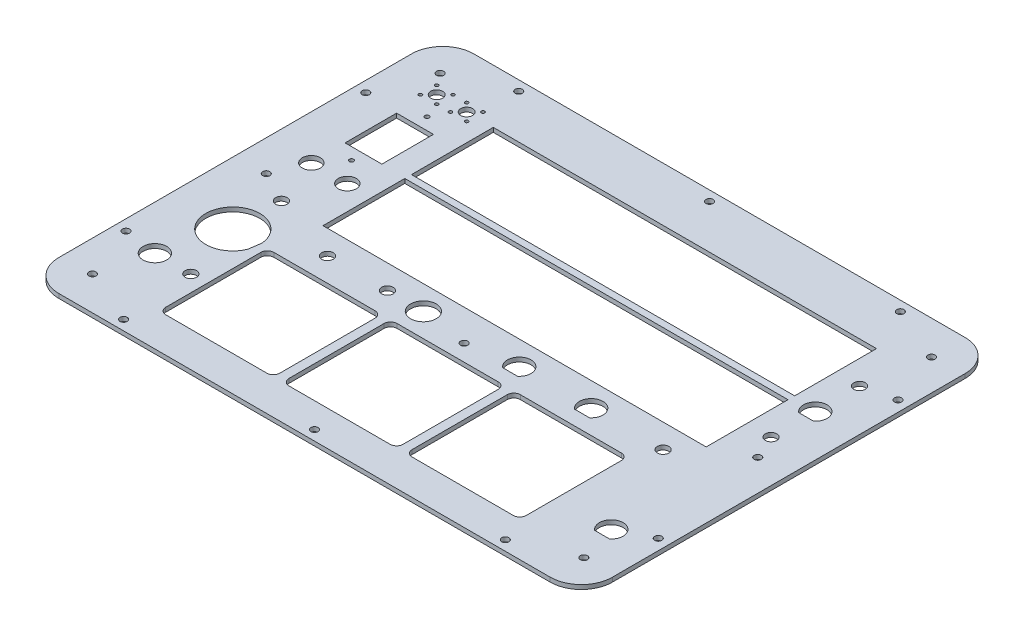
SolidWorks part; units mm, degrees
other "Markup1"
sketch "Sketch4" plane through (-146.6469, 2.286, -109.9312) normal (0, 1, 0) x (1, 0, 0)
other "DetailItem1"
other "DetailItem2"
other "DetailItem3"
other "Markup2"
sketch "Sketch5"
other "DetailItem4"
other "DetailItem5"
other "DetailItem6"
other "DetailItem7"
other "DetailItem8"
other "DetailItem9"
other "DetailItem1"
other "DetailItem2"
material "6061-T6 (SS)"
ref_plane "Front Plane" through (0, 0, 0) normal (0, 0, 1) x (1, 0, 0)
ref_plane "Top Plane" through (0, 0, 0) normal (0, 1, 0) x (1, 0, 0)
ref_plane "Right Plane" through (0, 0, 0) normal (1, 0, 0) x (0, 0, -1)
sketch "Sketch1" plane through (0, 0, 0) normal (0, 1, 0) x (1, 0, 0)
  line L1 (-146.6469, 109.9312) -> (146.6469, 109.9312)
  line L2 (-146.6469, 109.9312) -> (-146.6469, -109.9312)
  line L3 (-146.6469, -109.9312) -> (146.6469, -109.9312)
  line L4 (146.6469, 109.9312) -> (146.6469, -109.9312)
  line L5 (-146.6469, 109.9312) -> (146.6469, -109.9312) construction
  line L6 (-146.6469, -109.9312) -> (146.6469, 109.9312) construction
  point P0 (0, 0)
  dimension "D1" = 293.2938
  dimension "D2" = 219.8624
extrude "Boss-Extrude1" add sketch "Sketch1" along normal blind 2.286
fillet "Fillet1" radius 16.51 4 edges at (-146.6469, 1.143, -109.9312) (146.6469, 1.143, -109.9312) (-146.6469, 1.143, 109.9312) (146.6469, 1.143, 109.9312)
extrude "Cut-Extrude4" cut sketch "Sketch13" against normal through all
sketch "Sketch13" plane through (0, 2.286, -256.6474) normal (0, 1, 0) x (1, 0, 0)
  line L1 (-91.2749, -175.2912) -> (111.7219, -175.2912)
  line L2 (-91.2749, -175.2912) -> (-91.2749, -218.6236)
  line L3 (-91.2749, -218.6236) -> (111.7219, -218.6236)
  line L4 (111.7219, -175.2912) -> (111.7219, -218.6236)
  line L5 (-91.2749, -222.1636) -> (111.7219, -222.1636)
  line L6 (-91.2749, -222.1636) -> (-91.2749, -265.496)
  line L7 (-91.2749, -265.496) -> (111.7219, -265.496)
  line L8 (111.7219, -222.1636) -> (111.7219, -265.496)
sketch "Sketch3" plane through (0, 2.286, 0) normal (0, 1, 0) x (1, 0, 0)
  line L0 (111.7219, 34.4837) -> (124.4219, 36.2538) construction
  line L1 (124.4219, 36.2538) -> (111.7219, 38.0238) construction
  line L2 (-91.2749, -8.8487) -> (111.7219, -8.8487) construction
  line L3 (111.7219, 81.3562) -> (124.4219, 59.69) construction
  line L4 (124.4219, 59.69) -> (111.7219, 38.0238) construction
  line L5 (111.7219, 34.4837) -> (124.4219, 12.8175) construction
  line L6 (124.4219, 12.8175) -> (111.7219, -8.8487) construction
  line L7 (59.5622, -26.4001) -> (67.4378, -26.4001)
  line L12 (0, -1000) -> (0, 49000) construction
  line L13 (111.7219, 34.4837) -> (-91.2749, 34.4837) construction
  line L18 (21.4622, -26.4001) -> (29.3378, -26.4001)
  line L19 (120.4841, 31.4024) -> (128.3597, 31.4024)
  line L24 (120.4841, -76.6826) -> (128.3597, -76.6826)
  line L25 (-130.1369, -109.9312) -> (130.1369, -109.9312) construction
  line L26 (111.7219, -8.8487) -> (111.7219, 34.4837) construction
  arc A0 (128.3597, 31.4024) -> (120.4841, 31.4024) centre (124.4219, 36.2538) ccw
  circle A1 centre (124.4219, 59.69) radius 3.048
  circle A2 centre (124.4219, 12.8175) radius 3.048
  circle A3 centre (-76.2, -21.5487) radius 3.048
  circle A4 centre (-44.45, -21.5487) radius 3.048
  circle A5 centre (-25.4, -21.5487) radius 6.8
  arc A6 (128.3597, -76.6826) -> (120.4841, -76.6826) centre (124.4219, -71.8312) ccw
  arc A7 (29.3378, -26.4001) -> (21.4622, -26.4001) centre (25.4, -21.5487) ccw
  arc A8 (67.4378, -26.4001) -> (59.5622, -26.4001) centre (63.5, -21.5487) ccw
  circle A9 centre (25.4, -21.5487) radius 9.0043 construction
  circle A10 centre (63.5, -21.5487) radius 9.0043 construction
  circle A11 centre (101.6, -21.5487) radius 3.048
  point P20 (0, 0)
  point P44 (0, 0)
  dimension "D5" = 13.6
  dimension "D6" = 6.096
  dimension "D7" = 6.096
  dimension "D3" = 18.0086
  dimension "D4" = 12.4968
  dimension "D2" = 12.7
  dimension "D8" = 12.7
  dimension "D9" = 19.05
  dimension "D10" = 11.0998
  dimension "D11" = 25.4
  dimension "D12" = 38.1
  dimension "D13" = 38.1
  dimension "D14" = 38.1
  dimension "D15" = 76.2
  dimension "D16" = 25.4
sketch "Sketch8" plane through (0, 2.286, 0) normal (0, 1, 0) x (1, 0, 0)
  line L1 (-130.048, 99.441) -> (130.048, 99.441) construction
  line L2 (-135.89, 93.599) -> (-135.89, -93.599) construction
  line L3 (-130.048, -99.441) -> (130.048, -99.441) construction
  line L4 (135.89, 93.599) -> (135.89, -93.599) construction
  line L5 (-135.89, 99.441) -> (135.89, -99.441) construction
  line L6 (-135.89, -99.441) -> (135.89, 99.441) construction
  arc A0 (130.048, 99.441) -> (135.89, 93.599) centre (130.048, 93.599) cw construction
  arc A1 (130.048, -99.441) -> (135.89, -93.599) centre (130.048, -93.599) ccw construction
  arc A2 (-135.89, -93.599) -> (-130.048, -99.441) centre (-130.048, -93.599) ccw construction
  arc A3 (-130.048, 99.441) -> (-135.89, 93.599) centre (-130.048, 93.599) ccw construction
  point P0 (0, 0)
  dimension "D3" = 5.842
  dimension "D1" = 271.78
  dimension "D2" = 198.882
sketch "Sketch10" plane through (0, 2.286, 0) normal (0, 1, 0) x (1, 0, 0)
  line L2 (130.1369, 109.9312) -> (-130.1369, 109.9312) construction
  line L3 (-146.6469, 93.4212) -> (-146.6469, -93.4212) construction
  circle A0 centre (-121.2469, 81.3562) radius 3.175
  point P2 (-123.8756, 81.5186)
  dimension "D1" = 6.35
  dimension "D2" = 28.575
  dimension "D3" = 25.4
extrude "Cut-Extrude2" cut sketch "Sketch10" against normal through all
hole_wizard "#2-56 Tapped Hole1" positions "Sketch11" profile "Sketch12" tap size "#2-56" standard "ANSI Inch" end condition through all
sketch "Sketch11" plane through (0, 2.286, 0) normal (0, 1, 0) x (1, 0, 0)
  line L0 (-125.5649, 85.6742) -> (-116.9289, 77.0382) construction
  point P1 (-125.5649, 85.6742)
  point P2 (-116.9289, 77.0382)
  point P9 (-116.9289, 85.6742)
  point P11 (-125.5649, 77.0382)
  dimension "D1" = 8.636
  dimension "D2" = 8.636
sketch "Sketch12" plane through (-125.5649, 2.286, -85.6742) normal (1, 0, 0) x (0, 0, 1)
  line L0 (0, 0) -> (0, 2.286)
  line L1 (0, 2.286) -> (0.889, 2.286)
  line L2 (0.889, 2.286) -> (0.889, 0)
  line L5 (0.889, 0) -> (0, 0)
  line L11 (0, -6.35) -> (0, 107.95) construction
  dimension "Thru Tap Drill Dia." = 1.778
  dimension "Thru Tap Drill Depth" = 2.286
cosmetic thread "Hole Thread1" parameters "D2"=2.1844
cosmetic thread "Hole Thread2" parameters "D2"=2.1844
cosmetic thread "Hole Thread3" parameters "D2"=2.1844
cosmetic thread "Hole Thread4" parameters "D2"=2.1844
extrude "Cut-Extrude5" cut sketch "Sketch3" against normal through all
sketch "Sketch9" plane through (0, 2.286, 0) normal (0, 1, 0) x (1, 0, 0)
  line L1 (-130.048, 99.441) -> (130.048, 99.441) construction
  line L2 (-113.665, -1011.6034) -> (-113.665, 48988.3966) construction
  line L3 (-104.14, 16.891) -> (-113.665, 16.891) construction
  line L4 (-113.665, 16.891) -> (-123.19, 16.891) construction
  line L5 (-135.89, 93.599) -> (-135.89, -93.599) construction
  line L7 (-123.415, 62.291) -> (-103.915, 62.291)
  line L8 (-123.415, 62.291) -> (-123.415, 34.991)
  line L9 (-123.415, 34.991) -> (-103.915, 34.991)
  line L10 (-103.915, 62.291) -> (-103.915, 34.991)
  line L11 (-123.415, 62.291) -> (-103.915, 34.991) construction
  line L12 (-123.415, 34.991) -> (-103.915, 62.291) construction
  line L14 (-91.2749, -8.8487) -> (111.7219, -8.8487) construction
  line L15 (-99.4364, -32.9524) -> (-100.3898, -39.531)
  circle A0 centre (-123.19, 16.891) radius 4.7625
  circle A1 centre (-104.14, 16.891) radius 4.7625
  circle A2 centre (-113.665, -8.509) radius 3.048
  circle A3 centre (-76.2, -21.5487) radius 3.048 construction
  arc A5 (-99.4364, -32.9524) -> (-100.3898, -39.531) centre (-113.665, -34.2487) ccw
  circle A6 centre (-123.19, -65.9987) radius 6.2484
  circle A7 centre (25.4, -21.5487) radius 6.2484 construction
  circle A8 centre (-104.14, -65.9987) radius 3.048
  circle A9 centre (-44.45, -21.5487) radius 3.048 construction
  point P11 (-113.665, 48.641)
  point P34 (0, 0)
  point P35 (0, 0)
  dimension "D1" = 9.525
  dimension "D9" = 28.575
  dimension "D2" = 19.05
  dimension "D3" = 22.225
  dimension "D4" = 82.55
  dimension "D5" = 19.5
  dimension "D6" = 27.3
  dimension "D7" = 50.8
  dimension "D8" = 25.4
  dimension "D10" = 25.4
  dimension "D11" = 31.75
  dimension "D12" = 9.525
  dimension "D13" = 9.525
extrude "Cut-Extrude3" cut sketch "Sketch9" against normal through all
hole_wizard "#4-40 Tapped Hole1" positions "Sketch14" profile "Sketch15" tap size "#4-40" standard "ANSI Inch" end condition through all
sketch "Sketch14" plane through (0, 2.286, 0) normal (0, 1, 0) x (1, 0, 0)
  line L0 (-113.665, 28.641) -> (-113.665, 68.641)
  point P0 (-113.665, 28.641)
  point P2 (-113.665, 68.641)
  dimension "D1" = 40
sketch "Sketch15" plane through (-113.665, 2.286, -28.641) normal (1, 0, 0) x (0, 0, 1)
  line L0 (0, 0) -> (0, 2.286)
  line L1 (0, 2.286) -> (1.1303, 2.286)
  line L2 (1.1303, 2.286) -> (1.1303, 0)
  line L5 (1.1303, 0) -> (0, 0)
  line L11 (0, -6.35) -> (0, 107.95) construction
  dimension "Thru Tap Drill Dia." = 2.2606
  dimension "Thru Tap Drill Depth" = 2.286
cosmetic thread "Hole Thread9" parameters "D2"=2.8448
cosmetic thread "Hole Thread10" parameters "D2"=2.8448
hole_wizard "#6 Clearance Hole1" positions "Sketch16" profile "Sketch17" hole size "#6" standard "ANSI Inch" end condition through all
sketch "Sketch16" plane through (0, 2.286, -256.6474) normal (0, 1, 0) x (1, 0, 0)
  point P0 (0.0139, -152.0006)
  point P3 (-101.0781, -152.0006)
  point P6 (101.1059, -152.0006)
  point P9 (140.9839, -193.1486)
  point P12 (140.9839, -320.1486)
  point P15 (101.1059, -361.2966)
  point P18 (0.0139, -361.2966)
  point P21 (-101.0781, -361.2966)
  point P24 (-140.9561, -320.1486)
  point P27 (-140.9561, -193.1486)
sketch "Sketch17" plane through (0.0139, 2.286, -104.6468) normal (1, 0, 0) x (0, 0, 1)
  line L0 (0, 0) -> (0, 2.286)
  line L1 (0, 2.286) -> (1.8986, 2.286)
  line L2 (1.8986, 2.286) -> (1.8986, 0)
  line L3 (1.8986, 0) -> (0, 0)
  line L4 (0, -6.35) -> (0, 107.95) construction
  dimension "Thru Hole Dia." = 3.7973
  dimension "Thru Hole Depth" = 2.286
hole_wizard "#6 Clearance Hole2" positions "Sketch18" profile "Sketch19" hole size "#6" standard "ANSI Inch" end condition through all
sketch "Sketch18" plane through (0, 2.286, 0) normal (0, 1, 0) x (1, 0, 0)
  line L4 (-130.175, -92.075) -> (0, 0) construction
  line L5 (0, 0) -> (130.175, -92.075) construction
  line L7 (-130.175, 92.075) -> (0, 0) construction
  point P4 (-130.175, 0)
  point P21 (-130.175, -92.075)
  point P26 (-130.175, 92.075)
  point P28 (130.175, 92.075)
  point P30 (130.175, -92.075)
  point P58 (130.175, 0)
  point P60 (0, -25.4)
  dimension "D1" = 260.35
  dimension "D2" = 184.15
  dimension "D3" = 25.4
sketch "Sketch19" plane through (-130.175, 2.286, 0) normal (1, 0, 0) x (0, 0, 1)
  line L0 (0, 0) -> (0, 2.286)
  line L1 (0, 2.286) -> (1.8986, 2.286)
  line L2 (1.8986, 2.286) -> (1.8986, 0)
  line L5 (1.8986, 0) -> (0, 0)
  line L11 (0, -6.35) -> (0, 107.95) construction
  dimension "Thru Hole Dia." = 3.7973
  dimension "Thru Hole Depth" = 2.286
extrude "Cut-Extrude6" cut sketch "Sketch20" against normal through all
sketch "Sketch20" plane through (0, 2.286, -256.6474) normal (0, 1, 0) x (1, 0, 0)
  line L36 (-95.25, -294.1771) -> (-95.25, -344.5961) construction
  line L37 (-92.075, -347.7711) -> (-38.481, -347.7711) construction
  line L38 (-35.306, -344.5961) -> (-35.306, -294.1771) construction
  line L39 (-38.481, -291.0021) -> (-92.075, -291.0021) construction
  line L40 (-29.972, -294.1771) -> (-29.972, -344.5961) construction
  line L41 (26.797, -291.0021) -> (-26.797, -291.0021) construction
  line L42 (29.972, -344.5961) -> (29.972, -294.1771) construction
  line L43 (-26.797, -347.7711) -> (26.797, -347.7711) construction
  line L44 (35.306, -294.1771) -> (35.306, -344.5961) construction
  line L45 (92.075, -291.0021) -> (38.481, -291.0021) construction
  line L46 (95.25, -344.5961) -> (95.25, -294.1771) construction
  line L47 (38.481, -347.7711) -> (92.075, -347.7711) construction
  line L48 (-95.504, -294.1771) -> (-95.504, -344.5961)
  line L49 (-92.075, -348.0251) -> (-38.481, -348.0251)
  line L50 (-35.052, -344.5961) -> (-35.052, -294.1771)
  line L51 (-38.481, -290.7481) -> (-92.075, -290.7481)
  line L52 (-30.226, -294.1771) -> (-30.226, -344.5961)
  line L53 (-26.797, -348.0251) -> (26.797, -348.0251)
  line L54 (30.226, -344.5961) -> (30.226, -294.1771)
  line L55 (26.797, -290.7481) -> (-26.797, -290.7481)
  line L56 (35.052, -294.1771) -> (35.052, -344.5961)
  line L57 (38.481, -348.0251) -> (92.075, -348.0251)
  line L58 (95.504, -344.5961) -> (95.504, -294.1771)
  line L59 (92.075, -290.7481) -> (38.481, -290.7481)
  arc A36 (-92.075, -291.0021) -> (-95.25, -294.1771) centre (-92.075, -294.1771) ccw construction
  arc A37 (-95.25, -344.5961) -> (-92.075, -347.7711) centre (-92.075, -344.5961) ccw construction
  arc A38 (-38.481, -347.7711) -> (-35.306, -344.5961) centre (-38.481, -344.5961) ccw construction
  arc A39 (-35.306, -294.1771) -> (-38.481, -291.0021) centre (-38.481, -294.1771) ccw construction
  arc A40 (-26.797, -291.0021) -> (-29.972, -294.1771) centre (-26.797, -294.1771) ccw construction
  arc A41 (-29.972, -344.5961) -> (-26.797, -347.7711) centre (-26.797, -344.5961) ccw construction
  arc A42 (29.972, -294.1771) -> (26.797, -291.0021) centre (26.797, -294.1771) ccw construction
  arc A43 (26.797, -347.7711) -> (29.972, -344.5961) centre (26.797, -344.5961) ccw construction
  arc A44 (35.306, -344.5961) -> (38.481, -347.7711) centre (38.481, -344.5961) ccw construction
  arc A45 (38.481, -291.0021) -> (35.306, -294.1771) centre (38.481, -294.1771) ccw construction
  arc A46 (95.25, -294.1771) -> (92.075, -291.0021) centre (92.075, -294.1771) ccw construction
  arc A47 (92.075, -347.7711) -> (95.25, -344.5961) centre (92.075, -344.5961) ccw construction
  arc A48 (-95.504, -344.5961) -> (-92.075, -348.0251) centre (-92.075, -344.5961) ccw
  arc A49 (-38.481, -348.0251) -> (-35.052, -344.5961) centre (-38.481, -344.5961) ccw
  arc A50 (-35.052, -294.1771) -> (-38.481, -290.7481) centre (-38.481, -294.1771) ccw
  arc A51 (-92.075, -290.7481) -> (-95.504, -294.1771) centre (-92.075, -294.1771) ccw
  arc A52 (-30.226, -344.5961) -> (-26.797, -348.0251) centre (-26.797, -344.5961) ccw
  arc A53 (26.797, -348.0251) -> (30.226, -344.5961) centre (26.797, -344.5961) ccw
  arc A54 (30.226, -294.1771) -> (26.797, -290.7481) centre (26.797, -294.1771) ccw
  arc A55 (-26.797, -290.7481) -> (-30.226, -294.1771) centre (-26.797, -294.1771) ccw
  arc A56 (35.052, -344.5961) -> (38.481, -348.0251) centre (38.481, -344.5961) ccw
  arc A57 (92.075, -348.0251) -> (95.504, -344.5961) centre (92.075, -344.5961) ccw
  arc A58 (95.504, -294.1771) -> (92.075, -290.7481) centre (92.075, -294.1771) ccw
  arc A59 (38.481, -290.7481) -> (35.052, -294.1771) centre (38.481, -294.1771) ccw
pattern_linear "LPattern1" count 2 spacing 15.875 along (1, 0, 0) of "Cut-Extrude2", "#2-56 Tapped Hole1"
cosmetic thread "Hole Thread11" parameters "D2"=2.1844
cosmetic thread "Hole Thread12" parameters "D2"=2.1844
cosmetic thread "Hole Thread13" parameters "D2"=2.1844
cosmetic thread "Hole Thread14" parameters "D2"=2.1844
